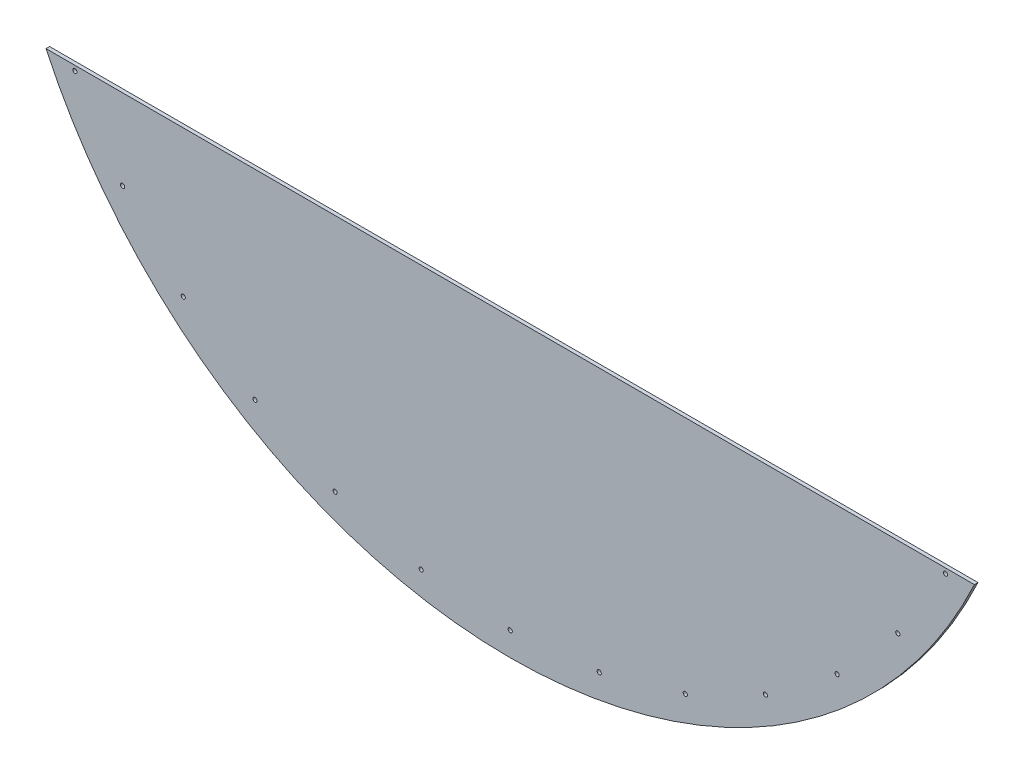
SolidWorks part; units mm, degrees
material "AISI 304"
ref_plane "Front Plane" through (0, 0, 0) normal (0, 0, 1) x (1, 0, 0)
ref_plane "Top Plane" through (0, 0, 0) normal (0, 1, 0) x (1, 0, 0)
ref_plane "Right Plane" through (0, 0, 0) normal (1, 0, 0) x (0, 0, -1)
sketch "Sketch1" plane through (0, 0, 0) normal (0, 0, 1) x (1, 0, 0)
  line L0 (859.9855, -5) -> (-859.9855, -5)
  arc A0 (-859.9855, -5) -> (859.9855, -5) centre (0, 0) ccw
  dimension "D1" = 1720
  dimension "D2" = 5
base flange "Base-Flange1" sketch "Sketch1" thickness 6 reverse thickness direction no parameters "D1"=0
sketch "Sketch2" plane through (0, 0, 0) normal (0, 0, 1) x (1, 0, 0)
  line L1 (-973.8714, 418.1233) -> (994.6473, 418.1233)
  line L2 (-973.8714, 418.1233) -> (-973.8714, -364)
  line L3 (-973.8714, -364) -> (994.6473, -364)
  line L4 (994.6473, 418.1233) -> (994.6473, -364)
  dimension "D1" = 364
extrude "Cut-Extrude1" cut sketch "Sketch2" against normal blind 10
sketch "Sketch3" plane through (0, 0, -6) normal (0, 0, -1) x (-1, 0, 0)
  circle A0 centre (0, -820) radius 3.5
  dimension "D1" = 7
  dimension "D2" = 820
extrude "Cut-Extrude2" cut sketch "Sketch3" against normal blind 10
pattern_circular "CirPattern4" count 7 every 10.5 about axis through (0, 0, 0) along (0, 0, 1) of "Cut-Extrude2"
sketch "Bend-Lines1" [suppressed] plane through (0, 0, 0) normal (0, 1, 0) x (1, 0, 0)
sketch "Bounding-Box1" [suppressed] plane through (0, 0, 0) normal (0, 1, 0) x (1, 0, 0)
sheet metal parameters "Sheet-Metal3" thickness 6 parameters "D1"=0
flat pattern "Flat-Pattern3" [suppressed]
sketch "Bend-Lines2" plane through (0, 0, 0) normal (0, 1, 0) x (1, 0, 0)
sketch3d "Bounding-Box2" [suppressed]
  line L0 (789.9842, -5, 0) -> (-789.9842, -5, 0) construction
  line L1 (789.9842, -789.9999, 0) -> (-789.9842, -789.9999, 0) construction
  line L2 (789.9842, -5, 0) -> (789.9842, -789.9999, 0) construction
  line L3 (-789.9842, -5, 0) -> (-789.9842, -789.9999, 0) construction
sheet metal parameters "Sheet-Metal4" thickness 6 parameters "D1"=0
flat pattern "Flat-Pattern3"
sketch "Bend-Lines2" plane through (0, 0, 0) normal (0, 1, 0) x (1, 0, 0)
sketch3d "Bounding-Box2" [suppressed]
  line L0 (-773.6466, -855, 0) -> (773.6466, -855, 0) construction
  line L1 (-773.6466, -364, 0) -> (773.6466, -364, 0) construction
  line L2 (-773.6466, -855, 0) -> (-773.6466, -364, 0) construction
  line L3 (773.6466, -855, 0) -> (773.6466, -364, 0) construction
sheet metal parameters "Sheet-Metal5" thickness 6 parameters "D1"=0
flat pattern "Flat-Pattern3"
sketch "Bend-Lines2" plane through (0, 0, 0) normal (0, 1, 0) x (1, 0, 0)
sketch3d "Bounding-Box2" [suppressed]
  line L0 (-773.6466, -855, 0) -> (773.6466, -855, 0) construction
  line L1 (-773.6466, -364, 0) -> (773.6466, -364, 0) construction
  line L2 (-773.6466, -855, 0) -> (-773.6466, -364, 0) construction
  line L3 (773.6466, -855, 0) -> (773.6466, -364, 0) construction
sheet metal parameters "Sheet-Metal6" thickness 6 parameters "D1"=0
flat pattern "Flat-Pattern3"
sketch "Bend-Lines2" plane through (0, 0, 0) normal (0, 1, 0) x (1, 0, 0)
sketch3d "Bounding-Box2" [suppressed]
  line L0 (-779.1688, -860, 0) -> (779.1688, -860, 0) construction
  line L1 (-779.1688, -364, 0) -> (779.1688, -364, 0) construction
  line L2 (-779.1688, -860, 0) -> (-779.1688, -364, 0) construction
  line L3 (779.1688, -860, 0) -> (779.1688, -364, 0) construction
